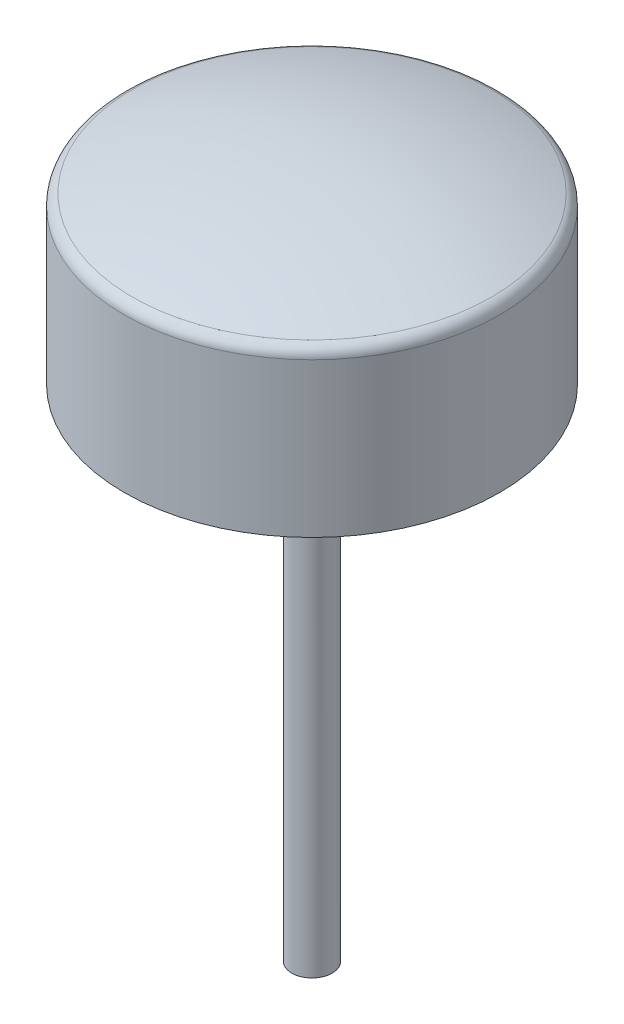
SolidWorks part; units mm, degrees
ref_plane "Front Plane" through (0, 0, 0) normal (0, 0, 1) x (1, 0, 0)
ref_plane "Top Plane" through (0, 0, 0) normal (0, 1, 0) x (1, 0, 0)
ref_plane "Right Plane" through (0, 0, 0) normal (1, 0, 0) x (0, 0, -1)
sketch "Sketch1" plane through (0, 0, 0) normal (0, 1, 0) x (1, 0, 0)
  line L0 (0, 0) -> (0, -37.1812) construction
  line L1 (0, 0) -> (-32.1999, 18.5906) construction
  line L2 (0, 0) -> (32.1999, 18.5906) construction
  point P7 (0, 0)
  dimension "D1" = 3
ref_plane "Plane1" through (0, 0, 0) normal (-0.7071, 0.7071, 0) x (0.7071, 0.7071, 0)
sketch "Sketch2" plane through (0, 0, 0) normal (-0.7071, 0.7071, 0) x (0.7071, 0.7071, 0)
  line L0 (0, 0) -> (0, -13.25)
  line L1 (0, 0) -> (16.7659, 4.4924)
  line L2 (16.7659, 5.9181) -> (16.7659, 3.4294)
  arc A0 (12.7985, 3.4294) -> (0, -13.25) centre (2.8952, -2.2216) cw
  point P4 (12.7985, 3.4294)
  dimension "D2" = 13.25
  dimension "D3" = 13.25
  dimension "D1" = 105
  dimension "D4" = 26.75
extrude "Boss-Extrude1" add sketch "Sketch2" along normal blind 1 contours A0 L1 L0 region at (4.7539, 4.7539, 5.1588)
ref_plane "Plane2" through (0, 0, 0) normal (0.3536, 0.7071, -0.6124) x (0.9268, -0.3536, 0.1268)
sketch "Sketch3" plane through (0, 0, 0) normal (0.3536, 0.7071, -0.6124) x (0.9268, -0.3536, 0.1268)
  line L0 (0, 0) -> (-14.3547, 8.2877)
  line L1 (0, 0) -> (-3.9956, -14.9117)
  arc A0 (-11.4621, 6.647) -> (-3.9956, -14.9117) centre (-0.2055, -1.5268) ccw
  point P2 (-11.4621, 6.647)
  point P3 (-3.4294, -12.7985)
  dimension "D1" = 13.25
  dimension "D2" = 105
  dimension "D3" = 13.25
  dimension "D4" = 26.75
extrude "Boss-Extrude2" add sketch "Sketch3" along normal blind 1 contours L0 A0 L1 region at (-6.5065, 5.012, 2.0308)
ref_plane "Plane3" through (0, 0, 0) normal (0.3536, 0.7071, 0.6124) x (0.9268, -0.3536, -0.1268)
sketch "Sketch4" plane through (0, 0, 0) normal (0.3536, 0.7071, 0.6124) x (0.9268, -0.3536, -0.1268)
  line L0 (0, 0) -> (10.8056, 6.2386)
  line L1 (0, 0) -> (-14.9102, 14.9102)
  arc A0 (-9.3692, 9.3692) -> (10.8056, 6.2386) centre (0.1782, 4.324) cw
  point P2 (-9.3692, 9.3692)
  point P4 (11.4748, 6.625)
  dimension "D1" = 105
  dimension "D2" = 13.25
  dimension "D3" = 13.25
  dimension "D4" = 26.75
extrude "Boss-Extrude3" add sketch "Sketch4" along normal blind 1 contours A0 L1 L0 region at (1.886, 4.8425, -6.6805)
sketch "Sketch5" plane through (0, 0, 0) normal (0, 1, 0) x (1, 0, 0)
  circle A0 centre (0, 0) radius 1.6589
extrude "Boss-Extrude4" add sketch "Sketch5" against normal blind 41 and the other way up to surface separate body other way up to face at (-3.8311, 3.127, 1.3988)
sketch "Sketch6" plane through (0, 0, 0) normal (0, 1, 0) x (1, 0, 0)
  circle A0 centre (0, 0) radius 14.3959
  circle A1 centre (0, 0) radius 15.3959
  dimension "D1" = 1
extrude "Boss-Extrude5" add sketch "Sketch6" along normal blind 12 separate body
sketch "Sketch7" plane through (0, 12, 0) normal (0, 1, 0) x (1, 0, 0)
  circle A0 centre (0, 0) radius 15.3959
extrude "Boss-Extrude6" add sketch "Sketch7" along normal blind 11
sketch "Sketch8" plane through (0, 0, 0) normal (0, 0, 1) x (1, 0, 0)
  line L0 (0, 16.1485) -> (0, 23.903)
  line L4 (0, 23.903) -> (16.2939, 23.903)
  line L5 (16.2939, 23.903) -> (16.2939, 12.9597)
  arc A1 (16.2939, 12.9597) -> (0, 16.1485) centre (0, -27.0745) ccw
revolve "Cut-Revolve2" cut sketch "Sketch8" angle 360 about L0
fillet "Fillet1" radius 1 1 edges at (0, 13.3136, -15.3959)
